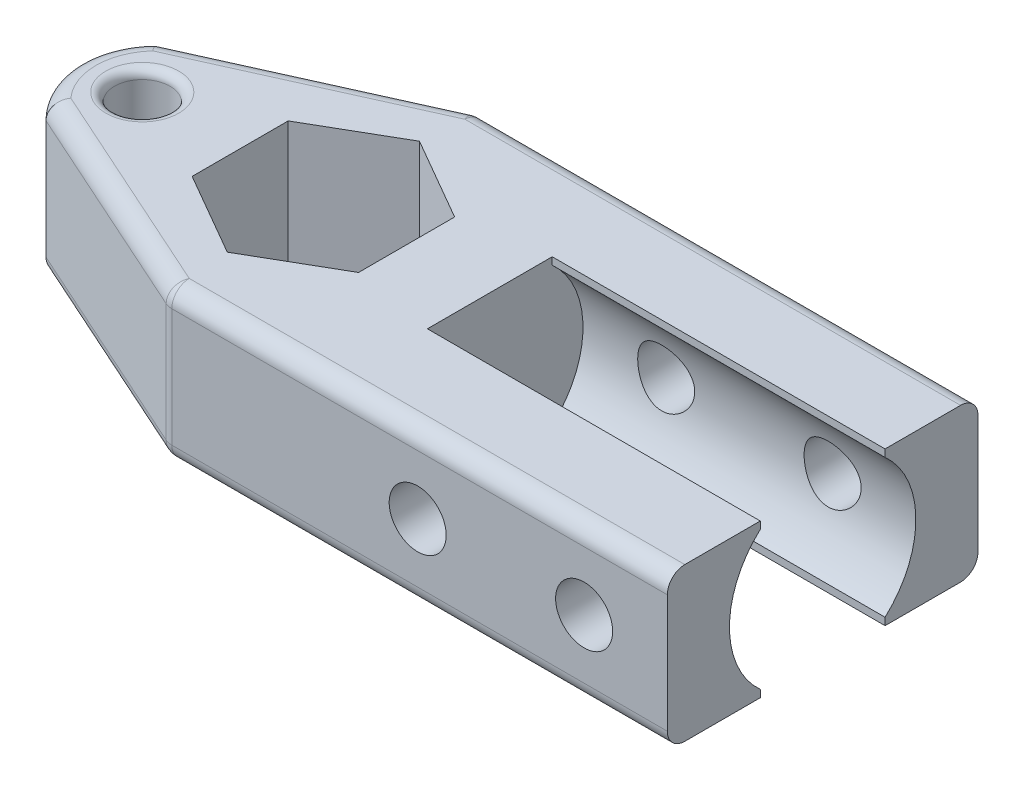
SolidWorks part; units mm, degrees
ref_plane "Front Plane" through (0, 0, 0) normal (0, 0, 1) x (1, 0, 0)
ref_plane "Top Plane" through (0, 0, 0) normal (0, 1, 0) x (1, 0, 0)
ref_plane "Right Plane" through (0, 0, 0) normal (1, 0, 0) x (0, 0, -1)
sketch "Sketch2" plane through (0, 0, 0) normal (0, 1, 0) x (1, 0, 0)
  line L0 (41.275, 0) -> (-41.275, 0) construction
  line L1 (31.75, -17.78) -> (-25.4, -17.78)
  line L3 (31.75, 17.78) -> (-25.4, 17.78)
  line L4 (-41.275, 0) -> (-60.325, 0) construction
  line L5 (41.275, -17.78) -> (-41.275, 17.78) construction
  line L6 (41.275, 17.78) -> (-41.275, -17.78) construction
  line L7 (-25.4, 17.78) -> (-25.4, -17.78) construction
  line L8 (31.75, 17.78) -> (31.75, -17.78)
  line L9 (-25.4, 10.9985) -> (-34.925, 5.4993)
  line L10 (-34.925, 5.4993) -> (-34.925, -5.4993)
  line L11 (-34.925, -5.4993) -> (-25.4, -10.9985)
  line L12 (-25.4, -10.9985) -> (-15.875, -5.4993)
  line L13 (-15.875, -5.4993) -> (-15.875, 5.4993)
  line L14 (-15.875, 5.4993) -> (-25.4, 10.9985)
  line L15 (-50.8, 6.35) -> (-25.4, 17.78)
  line L16 (-25.4, -17.78) -> (-50.8, -6.35)
  circle A0 centre (-25.4, 0) radius 9.525 construction
  arc A1 (-50.8, -6.35) -> (-50.8, 6.35) centre (-44.45, 0) cw
  circle A2 centre (-46.1277, 0) radius 3.175
  point P0 (0, 0)
  point P21 (-50.8, 0)
  dimension "D4" = 25.4
  dimension "D5" = 57.15
  dimension "D1" = 35.56
  dimension "D2" = 82.55
  dimension "D3" = 15.875
extrude "Boss-Extrude1" add sketch "Sketch2" along normal blind 17.526 contours A1 L16 L1 L3 L15 A2 region at (-3.1953, 0, 0)
fillet "Fillet4" radius 1 2 edges at (-46.1277, 0, 3.175) (-46.1277, 17.526, 3.175)
fillet "Fillet7" radius 2 6 edges at (-53.4303, 0, 0) (-38.1, 0, -12.065) (-38.1, 0, 12.065) (-38.1, 17.526, -12.065) (-53.4303, 17.526, 0) (-38.1, 17.526, 12.065)
sketch "Sketch5" plane through (31.75, 0, 0) normal (1, 0, 0) x (0, 0, -1)
  line L0 (-17.78, 8.763) -> (17.78, 8.763) construction
  line L1 (-17.78, 17.526) -> (-17.78, 0) construction
  line L2 (17.78, 17.526) -> (17.78, 0) construction
  line L3 (7.1438, 16.6859) -> (7.1438, 20.263)
  line L4 (7.1438, -2.737) -> (-7.1437, -2.737)
  line L5 (7.1438, -2.737) -> (7.1438, 0.8401)
  line L6 (7.1438, 20.263) -> (-7.1437, 20.263)
  line L7 (-7.1437, -2.737) -> (-7.1437, 0.8401)
  line L8 (7.1438, -2.737) -> (-7.1437, 20.263) construction
  line L9 (7.1438, 20.263) -> (-7.1437, -2.737) construction
  line L10 (-7.1437, 16.6859) -> (-7.1437, 20.263)
  arc A0 (-7.1437, 16.6859) -> (-7.1437, 0.8401) centre (0, 8.763) ccw
  arc A1 (7.1438, 0.8401) -> (7.1438, 16.6859) centre (0, 8.763) ccw
  dimension "D1" = 14.2875
extrude "Cut-Extrude3" cut sketch "Sketch5" against normal blind 38.1
sketch "Sketch6" plane through (0, 0, 17.78) normal (0, 0, 1) x (1, 0, 0)
  line L0 (31.75, 8.763) -> (-25.4, 8.763) construction
  line L1 (31.75, 17.526) -> (31.75, 0) construction
  line L2 (-25.4, 15.526) -> (-25.4, 2) construction
  circle A0 centre (3.175, 8.763) radius 3.2639
  circle A1 centre (22.225, 8.763) radius 3.2639
  dimension "D1" = 2
  dimension "D2" = 28.575
extrude "Cut-Extrude4" cut sketch "Sketch6" against normal through all
fillet "Fillet8" radius 2 10 edges at (5.6119, 0, -17.78) (-23.9725, 0.5858, -17.78) (-25.4, 8.763, -17.78) (-23.9725, 16.9402, -17.78) (5.6119, 0, 17.78) (-23.9725, 0.5858, 17.78) (-25.4, 8.763, 17.78) (-23.9725, 16.9402, 17.78) (5.6119, 17.526, -17.78) (5.6119, 17.526, 17.78)
